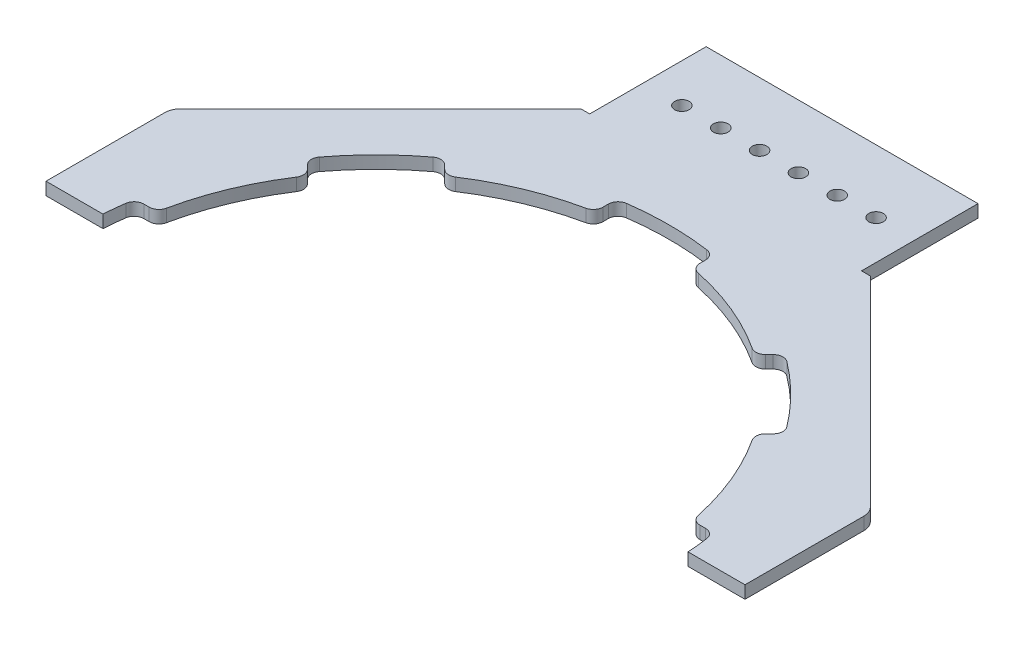
SolidWorks part; units mm, degrees
ref_plane "Front" through (0, 0, 0) normal (0, 0, 1) x (1, 0, 0)
ref_plane "Top" through (0, 0, 0) normal (0, 1, 0) x (1, 0, 0)
ref_plane "Right" through (0, 0, 0) normal (1, 0, 0) x (0, 0, -1)
sketch "Sketch1" plane through (0, 0, 0) normal (0, 1, 0) x (1, 0, 0)
  line L0 (14.1863, 2.5) -> (14.4624, 2.5)
  line L1 (15.0669, 1) -> (18, 1)
  line L2 (18, 1) -> (18, 7.1245)
  line L3 (17.7657, 7.6902) -> (7.4558, 18)
  line L4 (7.4558, 18) -> (7, 18)
  line L5 (7, 18) -> (7, 24)
  line L6 (7, 24) -> (-7, 24)
  line L7 (-7, 24) -> (-7, 18)
  line L8 (-7, 18) -> (-7.4558, 18)
  line L9 (-7.4558, 18) -> (-17.7657, 7.6902)
  line L10 (-18, 7.1245) -> (-18, 1)
  line L11 (-18, 1) -> (-15.0669, 1)
  line L12 (-14.4624, 2.5) -> (-14.1863, 2.5)
  line L13 (-11.799, 8.2634) -> (-11.9942, 8.4587)
  line L14 (-8.4587, 11.9942) -> (-8.2634, 11.799)
  line L15 (-2.5, 14.1863) -> (-2.5, 14.4624)
  line L16 (2.5, 14.4624) -> (2.5, 14.1863)
  line L17 (8.2634, 11.799) -> (8.4587, 11.9942)
  line L18 (11.9942, 8.4587) -> (11.799, 8.2634)
  line L19 (0, 24) -> (0, 0) construction
  line L20 (0, 0) -> (22.1606, 0) construction
  line L21 (0, 0) -> (12.7279, 12.7279) construction
  arc A0 (11.7335, 7.6371) -> (13.6971, 2.8966) centre (0, 0) cw
  arc A1 (13.6971, 2.8966) -> (14.1863, 2.5) centre (14.1863, 3) ccw
  arc A2 (14.4624, 2.5) -> (14.9577, 2.0685) centre (14.4624, 2) cw
  arc A3 (14.9577, 2.0685) -> (15.0669, 1) centre (0, 0) cw
  arc A4 (18, 7.1245) -> (17.7657, 7.6902) centre (17.2, 7.1245) ccw
  arc A5 (-17.7657, 7.6902) -> (-18, 7.1245) centre (-17.2, 7.1245) ccw
  arc A6 (-15.0669, 1) -> (-14.9577, 2.0685) centre (0, 0) cw
  arc A7 (-14.9577, 2.0685) -> (-14.4624, 2.5) centre (-14.4624, 2) cw
  arc A8 (-14.1863, 2.5) -> (-13.6971, 2.8966) centre (-14.1863, 3) ccw
  arc A9 (-13.6971, 2.8966) -> (-11.7335, 7.6371) centre (0, 0) cw
  arc A10 (-11.7335, 7.6371) -> (-11.799, 8.2634) centre (-12.1525, 7.9099) ccw
  arc A11 (-11.9942, 8.4587) -> (-12.0393, 9.114) centre (-11.6406, 8.8122) cw
  arc A12 (-12.0393, 9.114) -> (-9.114, 12.0393) centre (0, 0) cw
  arc A13 (-9.114, 12.0393) -> (-8.4587, 11.9942) centre (-8.8122, 11.6406) cw
  arc A14 (-8.2634, 11.799) -> (-7.6371, 11.7335) centre (-7.9099, 12.1525) ccw
  arc A15 (-7.6371, 11.7335) -> (-2.8966, 13.6971) centre (0, 0) cw
  arc A16 (-2.8966, 13.6971) -> (-2.5, 14.1863) centre (-3, 14.1863) ccw
  arc A17 (-2.5, 14.4624) -> (-2.0685, 14.9577) centre (-2, 14.4624) cw
  arc A18 (-2.0685, 14.9577) -> (2.0685, 14.9577) centre (0, 0) cw
  arc A19 (2.0685, 14.9577) -> (2.5, 14.4624) centre (2, 14.4624) cw
  arc A20 (2.5, 14.1863) -> (2.8966, 13.6971) centre (3, 14.1863) ccw
  arc A21 (2.8966, 13.6971) -> (7.6371, 11.7335) centre (0, 0) cw
  arc A22 (7.6371, 11.7335) -> (8.2634, 11.799) centre (7.9099, 12.1525) ccw
  arc A23 (8.4587, 11.9942) -> (9.114, 12.0393) centre (8.8122, 11.6406) cw
  arc A24 (9.114, 12.0393) -> (12.0393, 9.114) centre (0, 0) cw
  arc A25 (12.0393, 9.114) -> (11.9942, 8.4587) centre (11.6406, 8.8122) cw
  arc A26 (11.799, 8.2634) -> (11.7335, 7.6371) centre (12.1525, 7.9099) ccw
  dimension "D3" = 15.1
  dimension "D4" = 14
  dimension "D8" = 0.5
  dimension "D13" = 0.8
  dimension "D1" = 36
  dimension "D2" = 1
  dimension "D5" = 24
  dimension "D6" = 14
  dimension "D7" = 45
  dimension "D9" = 2.5
  dimension "D10" = 5
  dimension "D11" = 5
  dimension "D12" = 45
  dimension "D14" = 18
  dimension "D15" = 18
extrude "Boss-Extrude1" add sketch "Sketch1" against normal blind 0.65
sketch "Sketch2" plane through (0, 0, 0) normal (0, 1, 0) x (-1, 0, 0)
  line L0 (0, -23.5503) -> (0, 0) construction
  line L1 (0, 0) -> (-6.9273, 0) construction
  line L2 (5, -20.75) -> (-5, -20.75) construction
  circle A0 centre (-5, -20.75) radius 0.375
  circle A1 centre (3, -20.75) radius 0.375
  circle A2 centre (1, -20.75) radius 0.375
  circle A3 centre (-1, -20.75) radius 0.375
  circle A4 centre (-3, -20.75) radius 0.375
  circle A5 centre (5, -20.75) radius 0.375
  dimension "D5" = 0.75
  dimension "D1" = 20.75
  dimension "D2" = 10
  dimension "D3" = 2
  dimension "D4" = 6
extrude "Cut-Extrude1" cut sketch "Sketch2" against normal through all
sketch "Sketch3" plane through (0, -0.65, 0) normal (0, -1, 0) x (1, 0, 0)
  circle A0 centre (5, -20.75) radius 0.75
  dimension "D1" = 1.5
extrude "Boss-Extrude2" add sketch "Sketch3" along normal blind 0.2 separate body
dome "Dome1" faces to dome 1 distance 0.5 reverse direction no elliptical dome no face at (5, -0.85, -21.5) parameters "D1"=0.5
fillet "Fillet1" radius 0.4 1 edges at (5, -0.85, -21.5)
sketch "Sketch4" plane through (0, -0.65, 0) normal (0, 1, 0) x (1, 0, 0)
  line L0 (4.7348, 20.4848) -> (5.2652, 20.4848)
  line L1 (5.2652, 20.4848) -> (5.2652, 21.0152)
  line L2 (5.2652, 21.0152) -> (4.7348, 21.0152)
  line L3 (4.7348, 21.0152) -> (4.7348, 20.4848)
  circle A0 centre (5, 20.75) radius 0.375 construction
extrude "Cut-Extrude2" cut sketch "Sketch4" against normal through all
pattern_linear "LPattern1" count 6 spacing 2 along (-1, 0, 0) of bodies 107
combine bodies "Combine2" operation type add bodies to combine 112 111 110 109 108 107 105
